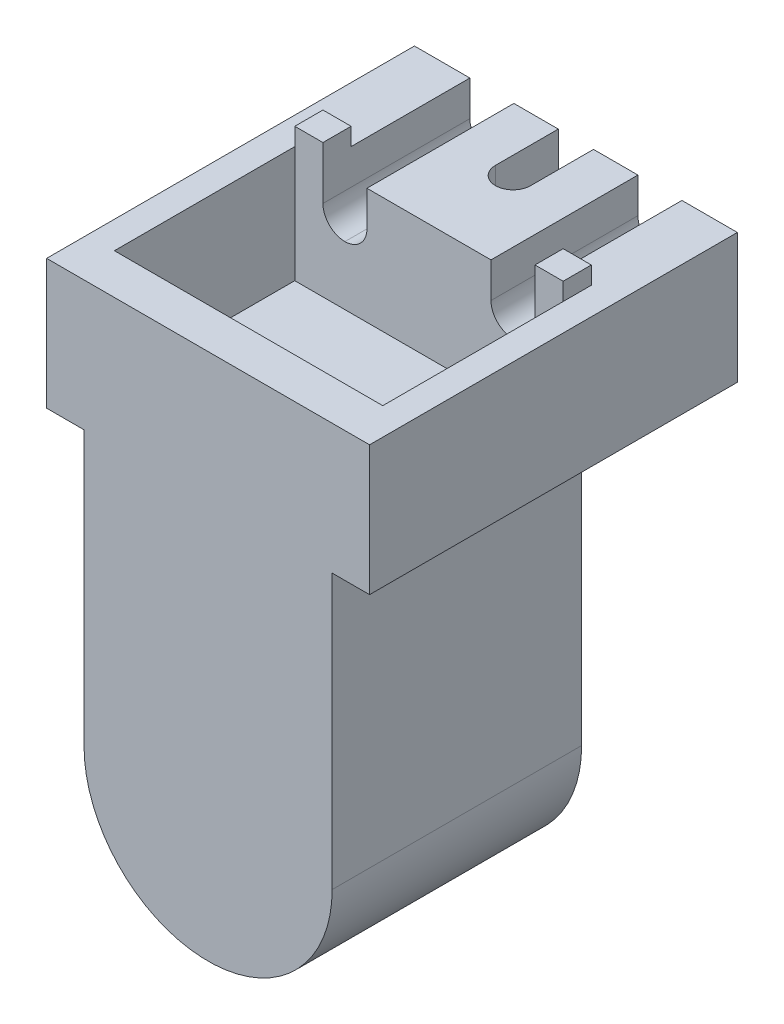
SolidWorks part; units mm, degrees
ref_plane "Plano frontal" through (0, 0, 0) normal (0, 0, 1) x (1, 0, 0)
ref_plane "Plano superior" through (0, 0, 0) normal (0, 1, 0) x (1, 0, 0)
ref_plane "Plano direito" through (0, 0, 0) normal (1, 0, 0) x (0, 0, -1)
sketch "Esboço1" plane through (0, 0, 0) normal (0, 0, 1) x (1, 0, 0)
  line L0 (0, 29.2752) -> (0, -37.2264) construction
  line L2 (14.1, -8.525) -> (14.1, 22.625)
  line L3 (14.1, 22.625) -> (-14.1, 22.625)
  line L4 (-14.1, -8.525) -> (-14.1, 22.625)
  line L5 (10.8926, -17.4783) -> (-14.1, 22.625) construction
  line L6 (14.1, 22.625) -> (-10.8926, -17.4783) construction
  arc A0 (-14.1, -8.525) -> (14.1, -8.525) centre (0, -8.525) ccw
  point P0 (0, 0)
extrude "Ressalto-extrusão1" add sketch "Esboço1" along normal blind 28.35
sketch "Esboço2" plane through (0, 0, 0) normal (0, 0, -1) x (-1, 0, 0)
  line L0 (0, -24.9025) -> (0, 25.4328) construction
  circle A0 centre (0, -13.375) radius 4.25
  arc A2 (-14.1, -8.525) -> (14.1, -8.525) centre (0, -8.525) ccw construction
  point P5 (0, -22.625)
  dimension "D1" = 8.5
  dimension "D2" = 9.25
extrude "Corte-extrusão1" cut sketch "Esboço2" against normal blind 26
sketch "Esboço3" plane through (0, 22.625, 0) normal (0, 1, 0) x (1, 0, 0)
  line L5 (0, 19.6491) -> (0, -44.0768) construction
  line L6 (14.1, -28.35) -> (-14.1, -28.35) construction
  line L7 (18.35, -28.35) -> (-18.35, -28.35)
  line L8 (18.35, -28.35) -> (18.35, 13.45)
  line L9 (18.35, 13.45) -> (-18.35, 13.45)
  line L10 (-18.35, -28.35) -> (-18.35, 13.45)
  line L11 (18.35, -28.35) -> (-18.35, 13.45) construction
  line L12 (18.35, 13.45) -> (-18.35, -28.35) construction
  point P2 (0, -7.45)
  dimension "D1" = 36.7
  dimension "D2" = 41.8
extrude "Ressalto-extrusão2" add sketch "Esboço3" along normal blind 14.75
sketch "Esboço5" plane through (0, 37.375, 0) normal (0, 1, 0) x (1, 0, 0)
  line L0 (0, 23.3821) -> (0, -37.1575) construction
  line L1 (-18.35, -28.35) -> (18.35, -28.35) construction
  line L2 (15.25, -23.75) -> (-15.25, -23.75)
  line L3 (15.25, -23.75) -> (15.25, -3.25)
  line L4 (15.25, -3.25) -> (-15.25, -3.25)
  line L5 (-15.25, -23.75) -> (-15.25, -3.25)
  line L6 (15.25, -23.75) -> (-15.25, -3.25) construction
  line L7 (15.25, -3.25) -> (-15.25, -23.75) construction
  point P3 (0, -13.5)
  dimension "D1" = 20.5
  dimension "D2" = 30.5
  dimension "D3" = 4.6
extrude "Corte-extrusão2" cut sketch "Esboço5" against normal blind 13.2
sketch "Esboço6" plane through (0, 37.375, 0) normal (0, 1, 0) x (1, 0, 0)
  line L0 (0, 19.3367) -> (0, -34.7053) construction
  line L1 (-2, 13.45) -> (-2, 6.3084)
  line L2 (18.35, 13.45) -> (-18.35, 13.45) construction
  line L3 (2, 13.45) -> (2, 6.3084)
  line L4 (-2, 13.45) -> (2, 13.45)
  arc A0 (-2, 6.3084) -> (2, 6.3084) centre (0, 6.3084) ccw
  dimension "D1" = 2
extrude "Corte-extrusão3" cut sketch "Esboço6" against normal through all
sketch "Esboço7" plane through (0, 37.375, 0) normal (0, 1, 0) x (1, 0, 0)
  line L0 (0, 21.5234) -> (0, -41.1091) construction
  line L1 (-12.05, 13.45) -> (-12.05, -3.25)
  line L2 (-2, 13.45) -> (-18.35, 13.45) construction
  line L3 (15.25, -3.25) -> (-15.25, -3.25) construction
  line L4 (-12.05, -3.25) -> (-7.05, -3.25)
  line L5 (-7.05, -3.25) -> (-7.05, 13.45)
  line L6 (-7.05, 13.45) -> (-12.05, 13.45)
  line L7 (-18.35, 13.45) -> (-18.35, -28.35) construction
  line L8 (7.05, -3.25) -> (7.05, 13.45)
  line L9 (12.05, -3.25) -> (7.05, -3.25)
  line L10 (12.05, 13.45) -> (12.05, -3.25)
  line L11 (7.05, 13.45) -> (12.05, 13.45)
  dimension "D1" = 6.3
  dimension "D2" = 5
extrude "Corte-extrusão4" cut sketch "Esboço7" against normal blind 6.5
fillet "Filete1" radius 2.5 4 edges at (-12.05, 30.875, -5.1) (-7.05, 30.875, -5.1) (7.05, 30.875, -5.1) (12.05, 30.875, -5.1)
sketch "Esboço8" plane through (0, 0, -13.45) normal (0, 0, -1) x (-1, 0, 0)
  line L0 (0, 41.7799) -> (0, 10.4982) construction
  line L1 (-21.2908, 30) -> (21.3757, 30) construction
  line L3 (4.2925, 28.25) -> (-4.2075, 28.25)
  line L4 (4.2925, 28.25) -> (4.2925, 31.75)
  line L5 (4.2925, 31.75) -> (-4.2075, 31.75)
  line L6 (-4.2075, 28.25) -> (-4.2075, 31.75)
  line L7 (4.2925, 28.25) -> (-4.2075, 31.75) construction
  line L8 (4.2925, 31.75) -> (-4.2075, 28.25) construction
  point P5 (0.0425, 30)
  dimension "D1" = 3.5
  dimension "D2" = 8.5
extrude "Corte-extrusão5" cut sketch "Esboço8" against normal blind 14
sketch "Esboço9" plane through (0, 37.375, 0) normal (0, 1, 0) x (1, 0, 0)
  line L0 (-12.05, 13.45) -> (-12.05, -3.25) construction
  line L1 (-15.25, -3.25) -> (-12.05, -3.25)
  line L2 (-15.25, -3.25) -> (-15.25, -0.05)
  line L3 (-15.25, -0.05) -> (-12.05, -0.05)
  line L4 (-12.05, -3.25) -> (-12.05, -0.05)
  line L5 (0, 16.9982) -> (0, -34.4251) construction
  line L6 (15.25, -0.05) -> (12.05, -0.05)
  line L7 (12.05, -3.25) -> (12.05, -0.05)
  line L8 (15.25, -3.25) -> (12.05, -3.25)
  line L9 (15.25, -3.25) -> (15.25, -0.05)
extrude "Ressalto-extrusão3" add sketch "Esboço9" along normal blind 2
